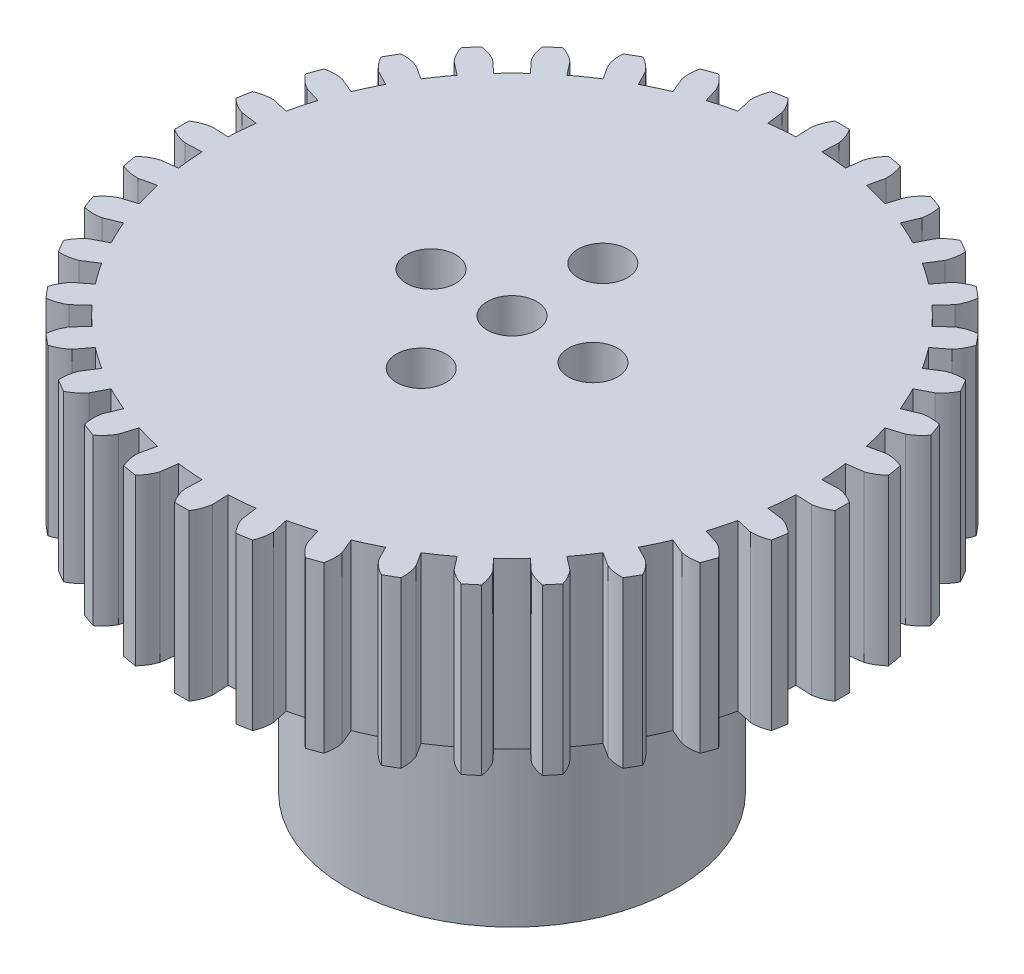
SolidWorks part; units mm, degrees
ref_plane "Front Plane" through (0, 0, 0) normal (0, 0, 1) x (1, 0, 0)
ref_plane "Top Plane" through (0, 0, 0) normal (0, 1, 0) x (1, 0, 0)
ref_plane "Right Plane" through (0, 0, 0) normal (1, 0, 0) x (0, 0, -1)
sketch "Sketch1" plane through (0, 0, 0) normal (0, 1, 0) x (1, 0, 0)
  line L0 (0, 0) -> (11.1857, 0) construction
  line L1 (0, 0) -> (12.1676, 1.0645) construction
  line L2 (0, 0) -> (13.2129, 0.5769) construction
  line L3 (0, 0) -> (12.0357, 0.2626) construction
  line L4 (17.9829, 0.7851) -> (18.9819, 0.8288)
  line L5 (0, 0) -> (17.9315, 1.5688)
  line L6 (17.9829, -0.7851) -> (18.9819, -0.8288)
  line L7 (0, 0) -> (17.9315, -1.5688)
  circle A0 centre (0, 0) radius 20 construction
  circle A1 centre (0, 0) radius 19 construction
  circle A2 centre (0, 0) radius 18 construction
  arc A3 (17.9829, 0.7851) -> (17.9315, 1.5688) centre (0, 0) ccw
  arc A5 (19.9952, -0.4363) -> (19.9952, 0.4363) centre (0, 0) ccw
  arc A7 (17.9829, -0.7851) -> (17.9315, -1.5688) centre (0, 0) cw
  arc A8 (18.9819, -0.8288) -> (19.9952, -0.4363) centre (18.619, 1.6127) ccw
  arc A9 (18.9819, 0.8288) -> (19.9952, 0.4363) centre (18.619, -1.6127) cw
  dimension "D4" = 40
  dimension "D5" = 1
  dimension "D6" = 1
  dimension "D1" = 5
  dimension "D2" = 2.5
  dimension "D3" = 1.25
extrude "Boss-Extrude1" add sketch "Sketch1" along normal blind 10
pattern_circular "CirPattern1" count 36 every 10 about axis through (0, 10, 0) along (0, -1, 0) of "Boss-Extrude1" reverse direction yes
sketch "Sketch2" plane through (0, 0, 0) normal (0, -1, 0) x (1, 0, 0)
  line L1 (2.3094, -4) -> (4.6188, 0)
  line L2 (4.6188, 0) -> (2.3094, 4)
  line L3 (2.3094, 4) -> (-2.3094, 4)
  line L4 (-2.3094, 4) -> (-4.6188, 0)
  line L5 (-4.6188, 0) -> (-2.3094, -4)
  line L6 (-2.3094, -4) -> (2.3094, -4)
  circle A0 centre (0, 0) radius 4 construction
  dimension "D1" = 8
sketch "Sketch4" plane through (0, 0, 0) normal (0, -1, 0) x (1, 0, 0)
  circle A0 centre (0, 0) radius 10
  dimension "D1" = 20
extrude "Boss-Extrude2" add sketch "Sketch4" along normal blind 15
sketch "Sketch3" plane through (0, 0, 0) normal (0, -1, 0) x (1, 0, 0)
  line L0 (0, 3) -> (0, 0) construction
  line L1 (2.4537, 7.25) -> (-2.4537, 7.25)
  line L2 (-2.4537, 7.25) -> (-4.9075, 3)
  line L3 (-4.9075, 3) -> (-2.4537, -1.25)
  line L4 (-2.4537, -1.25) -> (2.4537, -1.25)
  line L5 (2.4537, -1.25) -> (4.9075, 3)
  line L6 (4.9075, 3) -> (2.4537, 7.25)
  circle A0 centre (0, 3) radius 4.25 construction
  dimension "D1" = 8.5
  dimension "D2" = 3
extrude "Cut-Extrude1" [suppressed] cut sketch "Sketch3" against normal through all both and the other way through all
sketch "Sketch5" plane through (0, -15, 0) normal (0, -1, 0) x (1, 0, 0)
  line L0 (0, 0) -> (-4.905, 0) construction
  line L1 (0, 0) -> (4.905, 0) construction
  line L2 (0, 0) -> (0, 5.5) construction
  line L3 (0, 0) -> (0, -5.5) construction
  circle A0 centre (0, 0) radius 1.5
  circle A1 centre (-4.905, 0) radius 1.5
  circle A2 centre (4.905, 0) radius 1.5
  circle A3 centre (0, 5.5) radius 1.5
  circle A4 centre (0, -5.5) radius 1.5
  dimension "D1" = 3
  dimension "D2" = 4.905
  dimension "D3" = 5.5
extrude "Cut-Extrude2" cut sketch "Sketch5" against normal through all
